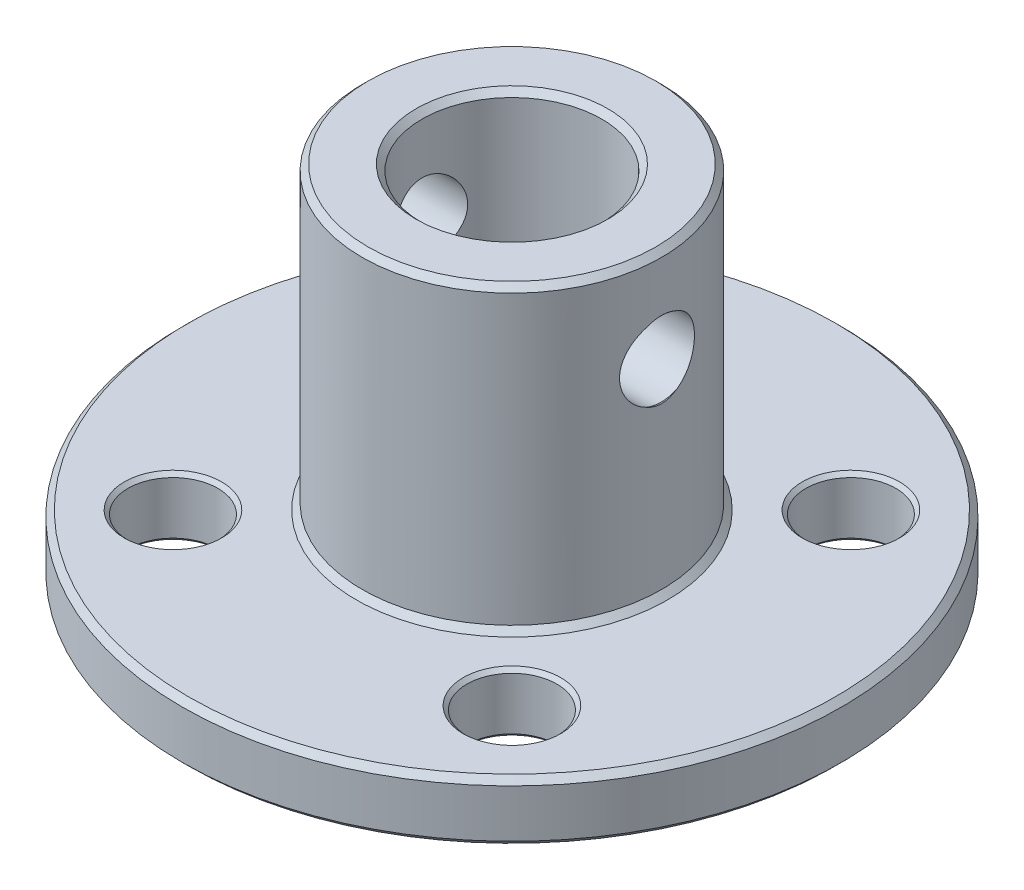
SolidWorks part; units mm, degrees
ref_plane "Front Plane" through (0, 0, 0) normal (0, 0, 1) x (1, 0, 0)
ref_plane "Top Plane" through (0, 0, 0) normal (0, 1, 0) x (1, 0, 0)
ref_plane "Right Plane" through (0, 0, 0) normal (1, 0, 0) x (0, 0, -1)
sketch "Sketch1" plane through (0, 0, 0) normal (0, 1, 0) x (1, 0, 0)
  circle A0 centre (0, 0) radius 11
  dimension "D1" = 22
extrude "Flange" add sketch "Sketch1" along normal blind 2
sketch "Sketch2" plane through (0, 2, 0) normal (0, 1, 0) x (1, 0, 0)
  circle A0 centre (0, 0) radius 5
  dimension "D1" = 10
extrude "Collar" add sketch "Sketch2" along normal blind 10
sketch "Sketch3" plane through (0, 12, 0) normal (0, 1, 0) x (1, 0, 0)
  circle A0 centre (0, 0) radius 3
  dimension "D1" = 6
extrude "Cut-Extrude1" cut sketch "Sketch3" against normal through all
sketch "Sketch4" plane through (0, 0, 0) normal (0, 0, 1) x (1, 0, 0)
  line L0 (5, 12) -> (-5, 12) construction
  line L1 (5, 2) -> (5, 12) construction
  line L2 (-5, 12) -> (-5, 2) construction
  point P0 (5, 8.85)
  point P1 (-5, 8.85)
  dimension "D1" = 3.15
hole_wizard "Set Screw Tap 1" positions "3DSketch1" profile "Sketch7" hole size "M3x0.5" standard "ANSI Metric" end condition up to next
sketch3d "3DSketch1"
  point P0 (5, 8.85, 0)
  point P3 (5, 8.85, 0)
  point P6 (5, 8.85, 0)
  point P8 (5, 8.85, 0)
  point P10 (5, 8.85, 0)
sketch "Sketch7" plane through (5, 8.85, 0) normal (0, 1, 0) x (0, 0, -1)
  line L0 (0, 0) -> (0, 5)
  line L1 (0, 5) -> (1.25, 5)
  line L2 (1.25, 5) -> (1.25, 0.025)
  line L3 (1.25, 0.025) -> (1.275, 0)
  line L5 (1.275, 0) -> (0, 0)
  line L6 (-1.25, 0.025) -> (-1.275, 0) construction
  line L11 (0, -6.35) -> (0, 107.95) construction
  dimension "Thru Hole Dia." = 2.5
  dimension "Thru Hole Depth" = 5
  dimension "Near C'Sink Dia." = 2.55
  dimension "Near C'Sink Angle" = 90
hole_wizard "Set Screw Tap 2" positions "3DSketch3" profile "Sketch9" hole size "M3x0.5" standard "ANSI Metric" end condition up to next
sketch3d "3DSketch3"
  point P0 (-5, 8.85, 0)
  point P4 (-5, 8.85, 0)
  point P7 (-5, 8.85, 0)
sketch "Sketch9" plane through (-5, 8.85, 0) normal (0, 1, 0) x (0, 0, 1)
  line L0 (0, 0) -> (0, 8.001)
  line L1 (0, 8.001) -> (1.25, 8.001)
  line L2 (1.25, 8.001) -> (1.25, 0.025)
  line L3 (1.25, 0.025) -> (1.275, 0)
  line L5 (1.275, 0) -> (0, 0)
  line L6 (-1.25, 0.025) -> (-1.275, 0) construction
  line L11 (0, -6.35) -> (0, 107.95) construction
  dimension "Thru Hole Dia." = 2.5
  dimension "Thru Hole Depth" = 8.001
  dimension "Near C'Sink Dia." = 2.55
  dimension "Near C'Sink Angle" = 90
sketch "Sketch10" plane through (0, 2, 0) normal (0, 1, 0) x (1, 0, 0)
  line L1 (-5.6569, -5.6569) -> (5.6569, -5.6569) construction
  line L2 (-5.6569, -5.6569) -> (-5.6569, 5.6569) construction
  line L3 (-5.6569, 5.6569) -> (5.6569, 5.6569) construction
  line L4 (5.6569, -5.6569) -> (5.6569, 5.6569) construction
  line L5 (-5.6569, -5.6569) -> (5.6569, 5.6569) construction
  line L6 (-5.6569, 5.6569) -> (5.6569, -5.6569) construction
  point P0 (0, 0)
  point P7 (-5.6569, 5.6569)
  point P8 (-5.6569, -5.6569)
  point P9 (5.6569, -5.6569)
  point P10 (5.6569, 5.6569)
  dimension "D1" = 16
hole_wizard "Flange Holes" positions "Sketch10" profile "Sketch11" hole size "M3" standard "ANSI Metric" end condition up to next
sketch "Sketch11" plane through (0, 2, 0) normal (1, 0, 0) x (0, 0, 1)
  line L0 (0, 0) -> (0, 2)
  line L1 (0, 2) -> (1.625, 2)
  line L2 (1.5, 1.875) -> (1.5, 0.125)
  line L3 (1.5, 0.125) -> (1.625, 0)
  line L5 (1.625, 0) -> (0, 0)
  line L6 (-1.5, 0.125) -> (-1.625, 0) construction
  line L7 (1.625, 2) -> (1.5, 1.875)
  line L8 (-1.625, 2) -> (-1.5, 1.875) construction
  line L11 (0, -6.35) -> (0, 107.95) construction
  dimension "Thru Hole Dia." = 3
  dimension "Thru Hole Depth" = 2
  dimension "Near C'Sink Dia." = 3.25
  dimension "Near C'Sink Angle" = 90
  dimension "Far C'Sink Dia." = 3.25
  dimension "Far C'Sink Angle" = 90
chamfer "Body Chamfers" distance 0.2 6 edges at (0, 2, 5) (0, 0, 3) (0, 12, 3) (0, 12, 5) (0, 0, 11) (0, 2, 11)
